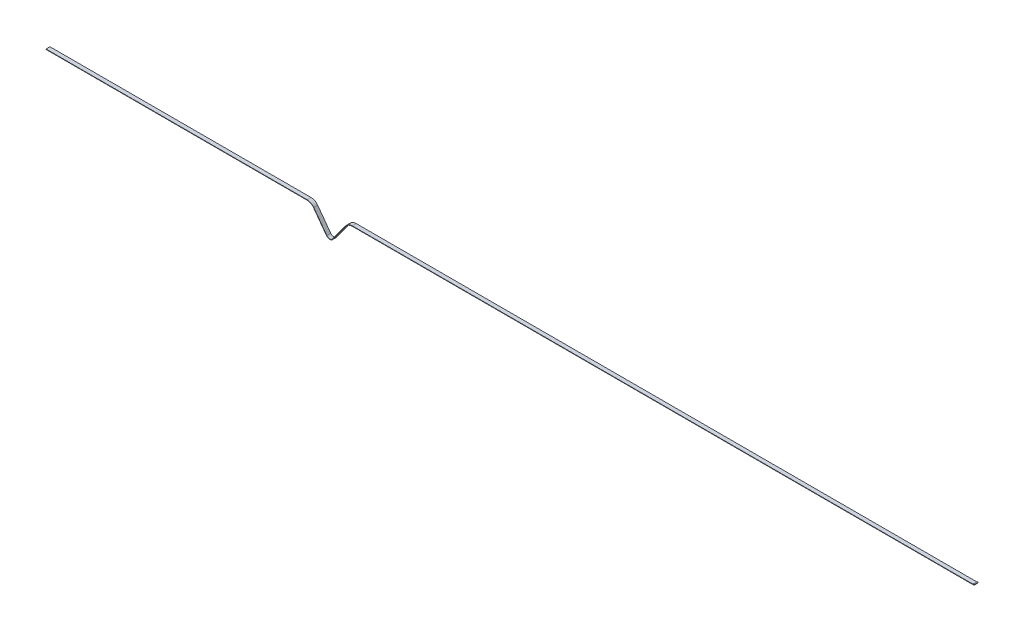
SolidWorks part; units mm, degrees
ref_plane "Front Plane" through (0, 0, 0) normal (0, 0, 1) x (1, 0, 0)
ref_plane "Top Plane" through (0, 0, 0) normal (0, 1, 0) x (1, 0, 0)
ref_plane "Right Plane" through (0, 0, 0) normal (1, 0, 0) x (0, 0, -1)
sketch "Sketch1" plane through (0, 0, 0) normal (1, 0, 0) x (0, 0, -1)
  line L1 (0, 0) -> (6, 0)
  line L2 (0, 0) -> (0, 0.63)
  line L3 (0, 0.63) -> (6, 0.63)
  line L4 (6, 0) -> (6, 0.63)
  dimension "D1" = 0.63
  dimension "D2" = 6
sketch "Sketch2" plane through (0, 0, 0) normal (0, 0, 1) x (1, 0, 0)
  line L0 (0, 0) -> (-953.0122, 0)
  line L1 (-962.6449, -4.8779) -> (-982.6571, -32.1359)
  line L2 (-992.5074, -32.1359) -> (-1012.5196, -4.8779)
  line L3 (-1022.1522, 0) -> (-1422.4, 0)
  arc A0 (-953.0122, 0) -> (-962.6449, -4.8779) centre (-953.0122, -11.95) ccw
  arc A1 (-982.6571, -32.1359) -> (-992.5074, -32.1359) centre (-987.5822, -28.52) cw
  arc A2 (-1012.5196, -4.8779) -> (-1022.1522, 0) centre (-1022.1522, -11.95) ccw
  circle A3 centre (-1022.1522, -11.95) radius 11.95 construction
  circle A4 centre (-987.5822, -28.52) radius 6.11 construction
  circle A5 centre (-953.0122, -11.95) radius 11.95 construction
  dimension "D1" = 6.11
  dimension "D4" = 1422.4
sweep "Sweep1" add profiles "Sketch1" path "Sketch2"
sketch "Sketch3" plane through (0, 0, 0) normal (0, 0, 1) x (1, 0, 0)
  line L0 (0, 0.63) -> (-953.0122, 0.63) construction
  line L1 (-1.5, 0.63) -> (-1.5, 0)
  line L2 (0, 0) -> (-953.0122, 0) construction
  line L3 (-1.5, 0) -> (0, 0)
  line L4 (0, 0) -> (0, 0.63)
  arc A1 (0, 0.63) -> (-1.5, 0.63) centre (-0.75, 0.63) ccw
  dimension "D1" = 0.75
extrude "Boss-Extrude1" add sketch "Sketch3" against normal through all
pattern_curve "CrvPattern1" [suppressed] of bodies 102 driven by "Sketch2" parameters "D1"=2000, "D3"=2, "D2"=1, "D4"=10
